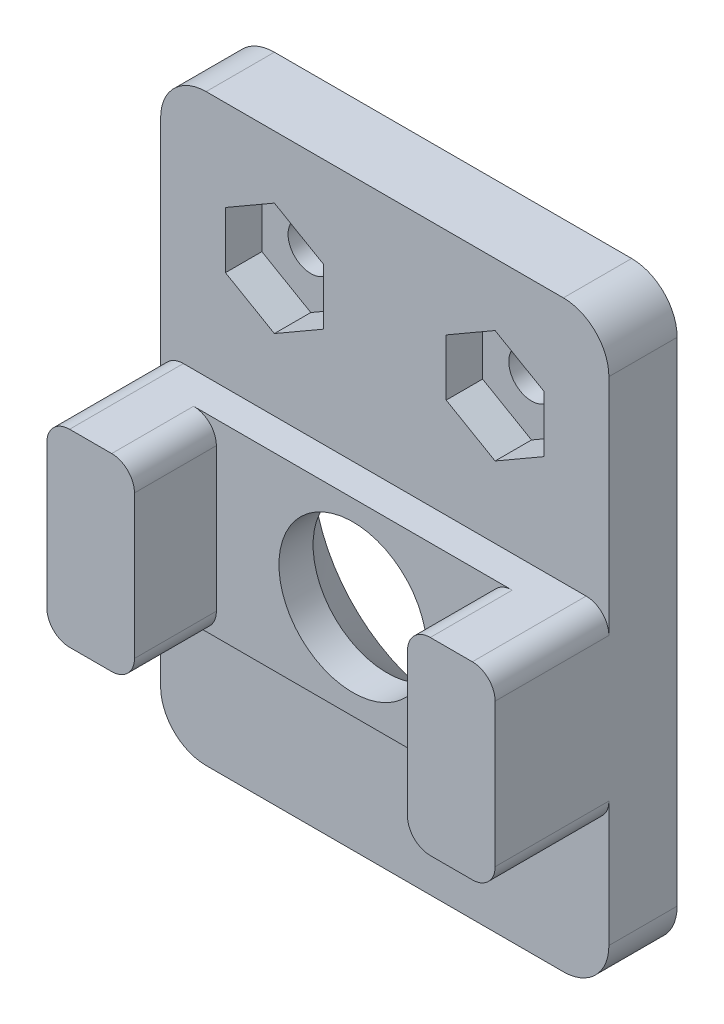
SolidWorks part; units mm, degrees
note: The reader was unsure of these and kept them because the rebuilt part matched: shared geometry of "Эскиз1<3>", "Эскиз1<4>", "Эскиз1<5>".
ref_plane "Спереди" through (0, 0, 0) normal (0, 0, 1) x (1, 0, 0)
ref_plane "Сверху" through (0, 0, 0) normal (0, 1, 0) x (1, 0, 0)
ref_plane "Справа" through (0, 0, 0) normal (1, 0, 0) x (0, 0, -1)
sketch "Эскиз1" plane through (0, 0, 0) normal (0, 0, 1) x (1, 0, 0)
  line L0 (15.6905, 18) -> (-11.1153, 18) construction
  line L1 (-0.884, 4.15) -> (-0.884, -4.15)
  line L2 (-0.884, 4.15) -> (2.966, 4.15)
  line L3 (2.966, 4.15) -> (2.966, -4.15)
  line L4 (-0.884, -4.15) -> (2.966, -4.15)
  line L5 (4.116, 9.7744) -> (13.816, 9.7744) construction
  line L6 (8.966, 0) -> (8.966, 16.9836) construction
  line L7 (2.966, 4.15) -> (14.966, 4.15)
  line L8 (2.966, -4.15) -> (14.966, -4.15)
  line L10 (4.116, 12.257) -> (1.966, 11.0157)
  line L11 (1.966, 11.0157) -> (1.966, 8.5331)
  line L12 (1.966, 8.5331) -> (4.116, 7.2918)
  line L13 (4.116, 7.2918) -> (6.266, 8.5331)
  line L14 (6.266, 8.5331) -> (6.266, 11.0157)
  line L15 (6.266, 11.0157) -> (4.116, 12.257)
  line L16 (13.816, 12.257) -> (11.666, 11.0157)
  line L17 (11.666, 11.0157) -> (11.666, 8.5331)
  line L18 (11.666, 8.5331) -> (13.816, 7.2918)
  line L19 (13.816, 7.2918) -> (15.966, 8.5331)
  line L20 (15.966, 8.5331) -> (15.966, 11.0157)
  line L21 (4.116, 6.7994) -> (4.116, 10.2432) construction
  line L22 (13.816, 6.7994) -> (13.816, 10.2432) construction
  line L23 (2.966, 0) -> (14.966, 0)
  line L24 (15.966, 11.0157) -> (13.816, 12.257)
  line L25 (14.966, -4.15) -> (18.816, -4.15)
  line L26 (14.966, -4.15) -> (14.966, 4.15)
  line L27 (14.966, 4.15) -> (18.816, 4.15)
  line L28 (18.816, -4.15) -> (18.816, 4.15)
  line L29 (-0.884, 15) -> (18.816, 15)
  line L30 (-0.884, 15) -> (-0.884, -10.65)
  line L31 (-0.884, -10.65) -> (18.816, -10.65)
  line L32 (18.816, 15) -> (18.816, -10.65)
  circle A0 centre (4.116, 9.7744) radius 2.15 construction
  circle A1 centre (13.816, 9.7744) radius 2.15 construction
  circle A4 centre (4.116, 9.7744) radius 1
  circle A5 centre (13.816, 9.7744) radius 1
  circle A6 centre (8.966, 0) radius 3.25
  point P0 (0, 0)
  point P8 (8.966, 9.7744)
  point P40 (4.116, 8.7744)
  point P41 (13.816, 8.7744)
  dimension "D8" = 2
  dimension "D9" = 2
  dimension "D12" = 15
  dimension "D1" = 18
  dimension "D2" = 8.3
  dimension "D3" = 6
  dimension "D4" = 19.7
  dimension "D13" = 10.65
  dimension "D14" = 6
  dimension "D15" = 9.7
extrude "Бобышка-Вытянуть1" add sketch "Эскиз1" along normal blind 3 contours A6 L23 L26 L27 L32 L29 L30 L2 L3 A5 A4 | A6 L23 L3 L4 L30 L31 L32 L25 L26 | L25 L28 L27 L26 | L1 L4 L3 L2 | A6 L23 L3 L8 L26 | A6 L23 L26 L7 L3 | L14 L15 L10 L11 L12 L13 A4 | L20 L24 L16 L17 L18 L19 A5
extrude "Бобышка-Вытянуть2" add sketch "Эскиз1<3>" along normal blind 8 contours L1 L4 L3 L2 | L25 L28 L27 L26
sketch "Эскиз1<3>" plane through (0, 0, 0) normal (0, 0, 1) x (1, 0, 0) same geometry as "Эскиз1"
fillet "Скругление1" radius 2 4 edges at (18.816, -10.65, 1.5) (-0.884, -10.65, 1.5) (-0.884, 15, 1.5) (18.816, 15, 1.5)
chamfer "Фаска1" distance 2.9 angle 45 1 edges at (12.216, 0, 0)
fillet "Скругление2" radius 1 4 edges at (18.816, 4.15, 5.5) (-0.884, 4.15, 5.5) (-0.884, -4.15, 5.5) (18.816, -4.15, 5.5)
extrude "Бобышка-Вытянуть4" add sketch "Эскиз1<4>" along normal blind 1.4 from vertex at 3 contours A6 L23 L3 L8 L26 | A6 L23 L26 L7 L3
sketch "Эскиз1<4>" plane through (0, 0, 0) normal (0, 0, 1) x (1, 0, 0) same geometry as "Эскиз1"
fillet "Скругление3" radius 1 4 edges at (2.966, -4.15, 6.2) (14.966, -4.15, 6.2) (14.966, 4.15, 6.2) (2.966, 4.15, 6.2)
extrude "Вырез-Вытянуть1" cut sketch "Эскиз1<5>" against normal blind 1.6 from vertex contours L14 L15 L10 L11 L12 L13 A4 | L20 L24 L16 L17 L18 L19 A5
sketch "Эскиз1<5>" plane through (0, 0, 0) normal (0, 0, 1) x (1, 0, 0) same geometry as "Эскиз1"
